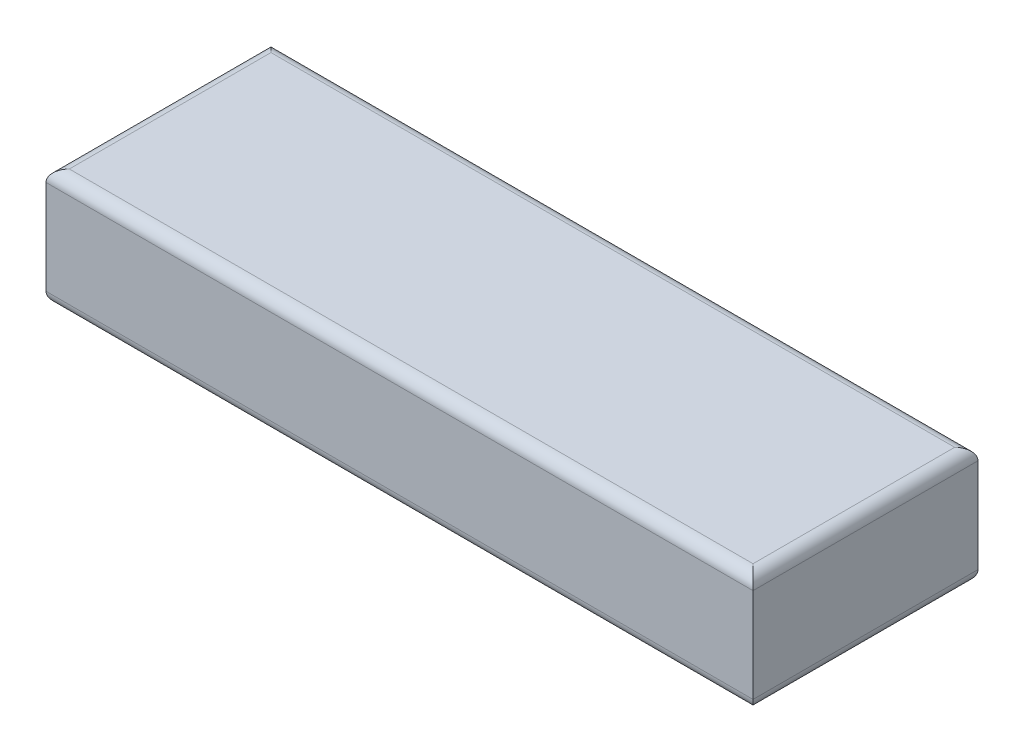
SolidWorks part; units mm, degrees
ref_plane "Front Plane" through (0, 0, 0) normal (0, 0, 1) x (1, 0, 0)
ref_plane "Top Plane" through (0, 0, 0) normal (0, 1, 0) x (1, 0, 0)
ref_plane "Right Plane" through (0, 0, 0) normal (1, 0, 0) x (0, 0, -1)
sketch "Sketch1" plane through (0, 0, 0) normal (0, 1, 0) x (1, 0, 0)
  line L1 (-2.7063, -52.4148) -> (151.2937, -52.4148)
  line L2 (-2.7063, -52.4148) -> (-2.7063, -3.4148)
  line L3 (-2.7063, -3.4148) -> (151.2937, -3.4148)
  line L4 (151.2937, -52.4148) -> (151.2937, -3.4148)
  dimension "D1" = 49
  dimension "D2" = 154
extrude "Boss-Extrude1" add sketch "Sketch1" along normal blind 25.6
fillet "Fillet1" radius 2.54 8 edges at (74.2937, 0, 3.4148) (151.2937, 0, 27.9148) (74.2937, 0, 52.4148) (-2.7063, 0, 27.9148) (74.2937, 25.6, 52.4148) (151.2937, 25.6, 27.9148) (74.2937, 25.6, 3.4148) (-2.7063, 25.6, 27.9148)
